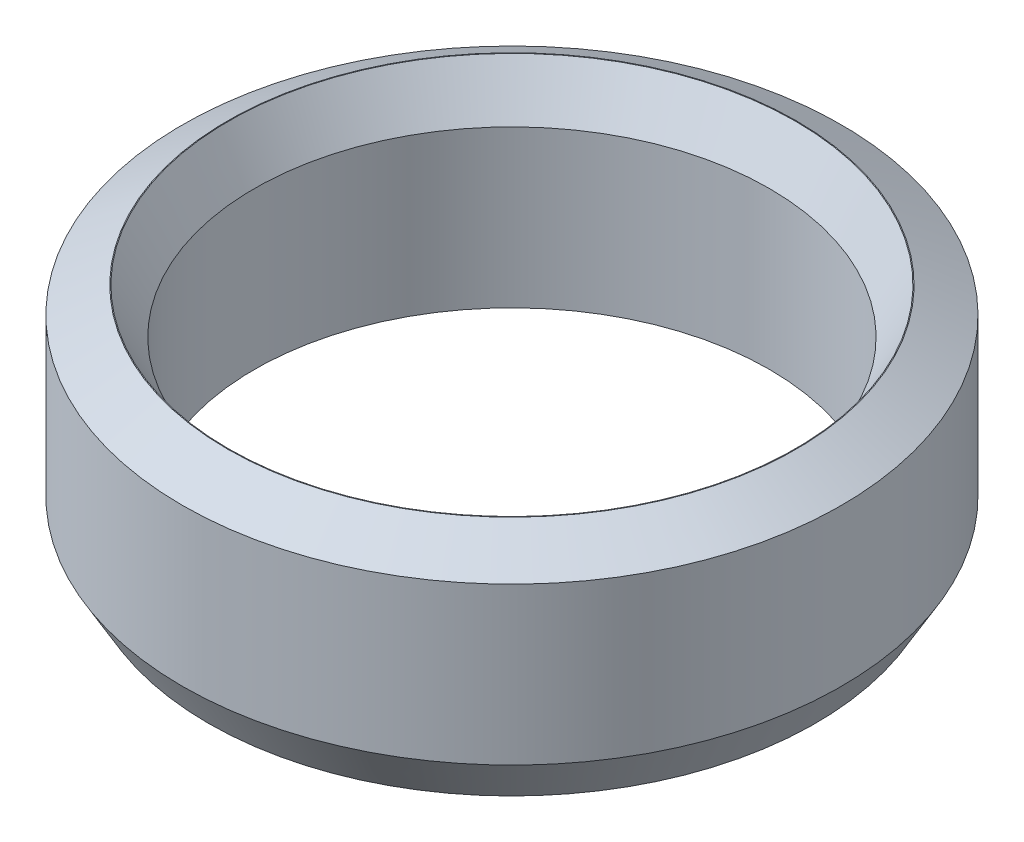
SolidWorks part; units mm, degrees
ref_plane "Front Plane" through (0, 0, 0) normal (0, 0, 1) x (1, 0, 0)
ref_plane "Top Plane" through (0, 0, 0) normal (0, 1, 0) x (1, 0, 0)
ref_plane "Right Plane" through (0, 0, 0) normal (1, 0, 0) x (0, 0, -1)
sketch "Sketch1" plane through (0, 0, 0) normal (0, 1, 0) x (1, 0, 0)
  circle A0 centre (0, 0) radius 32.5
  dimension "SLEEVE_OD" = 65
extrude "Boss-Extrude1" add sketch "Sketch1" along normal blind 22.4825
sketch "Sketch2" plane through (0, 0, 0) normal (0, 1, 0) x (1, 0, 0)
  circle A0 centre (0, 0) radius 25.3939
  dimension "BORE_D" = 50.7879
extrude "Cut-Extrude1" cut sketch "Sketch2" along normal through all
chamfer "Chamfer1" distance 2.5727 angle 60 4 edges at (0, 22.4825, 25.3939) (0, 0, 25.3939) (0, 0, 32.5) (0, 22.4825, 32.5) first distance on face at (0, 22.4825, 25.3939) first distance on face at (0, 0, 25.3939) first distance on face at (0, 22.4825, 32.5)
